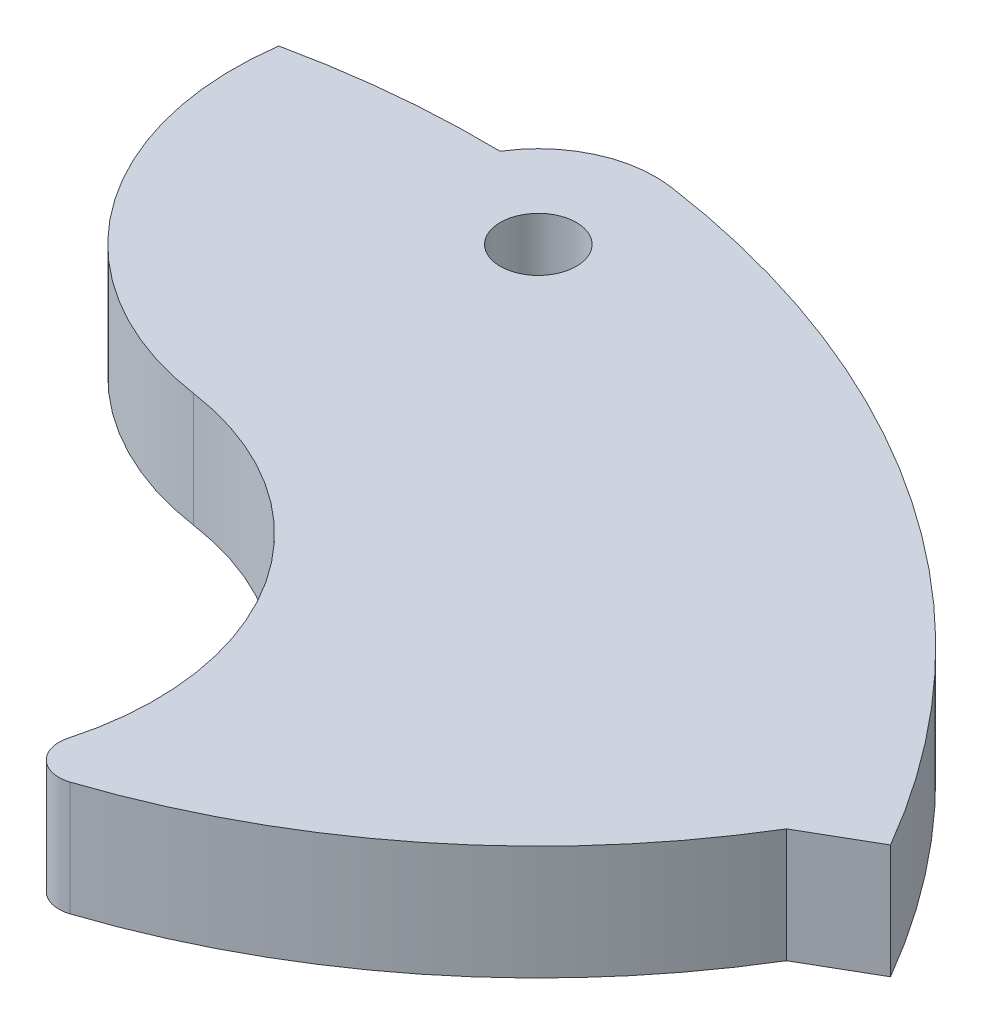
SolidWorks part; units mm, degrees
ref_plane "Front Plane" through (0, 0, 0) normal (0, 0, 1) x (1, 0, 0)
ref_plane "Top Plane" through (0, 0, 0) normal (0, 1, 0) x (1, 0, 0)
ref_plane "Right Plane" through (0, 0, 0) normal (1, 0, 0) x (0, 0, -1)
sketch "Sketch1" plane through (0, 0, 0) normal (0, 1, 0) x (1, 0, 0)
  line L2 (0, 97.8878) -> (0, 0) construction
  line L3 (0, 0) -> (88.0231, 50.8201) construction
  line L6 (67.8609, 39.1795) -> (62.3616, 36.0045)
  arc A1 (11.1734, 77.5583) -> (67.8609, 39.1795) centre (0, 0) cw
  circle A2 centre (9.779, 67.8792) radius 3.175
  circle A6 centre (0, 0) radius 25.4 construction
  arc A15 (62.3616, 36.0045) -> (29.0883, 9.5004) centre (9.779, 67.8792) cw
  arc A16 (11.1734, 77.5583) -> (1.4544, 73.0105) centre (9.779, 67.8792) ccw
  arc A17 (6.1571, 42.7388) -> (-15.3775, 71.3875) centre (9.779, 67.8792) cw
  circle A18 centre (4.8895, 33.9396) radius 8.89 construction
  arc A19 (6.1571, 42.7388) -> (25.8432, 12.5913) centre (2.7379, 19.0049) cw
  arc A20 (-15.3775, 71.3875) -> (1.4544, 73.0105) centre (0, 0) cw
  arc A21 (29.0883, 9.5004) -> (25.8432, 12.5913) centre (28.2907, 11.912) cw
  point P1 (-15.3775, 71.3875)
  point P13 (6.1571, 42.7388)
  point P15 (6.1571, 42.7388)
  point P16 (0, 0)
  point P19 (1.4001, 72.9924)
  point P21 (2.7379, 72.9213)
  point P23 (4.8895, 33.9396)
  point P24 (-15.3775, 71.3493)
  point P27 (24.0817, 8.0765)
  dimension "D1" = 78.359
  dimension "D4" = 6.35
  dimension "D8" = 50.8
  dimension "D9" = 25.4
  dimension "D11" = 17.78
  dimension "D7" = 73.025
  dimension "D10" = 2.54
  dimension "D5" = 68.58
  dimension "D2" = 72.009
  dimension "D6" = 60
  dimension "D3" = 9.779
  dimension "D12" = 34.29
extrude "Boss-Extrude1" add sketch "Sketch1" along normal blind 9.525
equation "\"AB_Coupler_OD_Length\"= 1in"
equation "\"AB_Coupling_Section_Length\"= 0.375in"
equation "\"AB_Coupler_Length\"= \"AB_Coupler_OD_Length\" + \"AB_Coupling_Section_Length\" * 2"
equation "\"AB_Coupler_Num_Screws\"= 6"
equation "\"Cutout_Angle\" = 60"
equation "\"AB_Coupling_Screw_Diameter\"= 0.1065in"
equation "\"Aft_Section_Length\"= 40in"
equation "\"Aft_Lower_Length\"= 20in"
equation "\"Aft_Upper_Length\"= \"Aft_Section_Length\" - \"Aft_Lower_Length\" - \"AB_Coupler_OD_Length\""
equation "\"Num_Cutouts\" = 4"
equation "\"Mid_Coupler_Length\" = 10in"
equation "\"Lead_Screw_Dist\" = 2.25in"
equation "\"Lead_Screw_Diam\" = (27/64)*1in"
equation "\"Lead_Screw_Length\" = (\"Mid_Coupler_Length\" + 2*0.375in + 2*0.5in)"
equation "\"Bodytube_OD\" = 6.17in"
equation "\"D1@Sketch1\"=\"Bodytube_OD\"/2"
equation "\"Paddle_Pin_Offset\" = \"Bodytube_OD\"/2-\"Paddle_Pin_Radius\""
equation "\"D5@Sketch1\"=2.7in"
equation "\"D2@Sketch1\"=\"Bodytube_OD\"/2-.25"
equation "\"D6@Sketch1\"=\"Cutout_Angle\""
equation "\"Paddle_Pin_Radius\" = 2.7in"
equation "\"AB_Coupler_OD\"= 6.17in"
equation "\"AB_Coupler_ID\"= 5.75in"
equation "\"AB_Coupler_Surface_Diameter\"= 5.998in"
equation "\"Bodytube_ID\" = 5.998in"
equation "\"D3@Sketch1\"=\"Paddle_Pin_Offset\""
equation "\"D7@Sketch1\"=\"AB_Coupler_ID\"/2"
